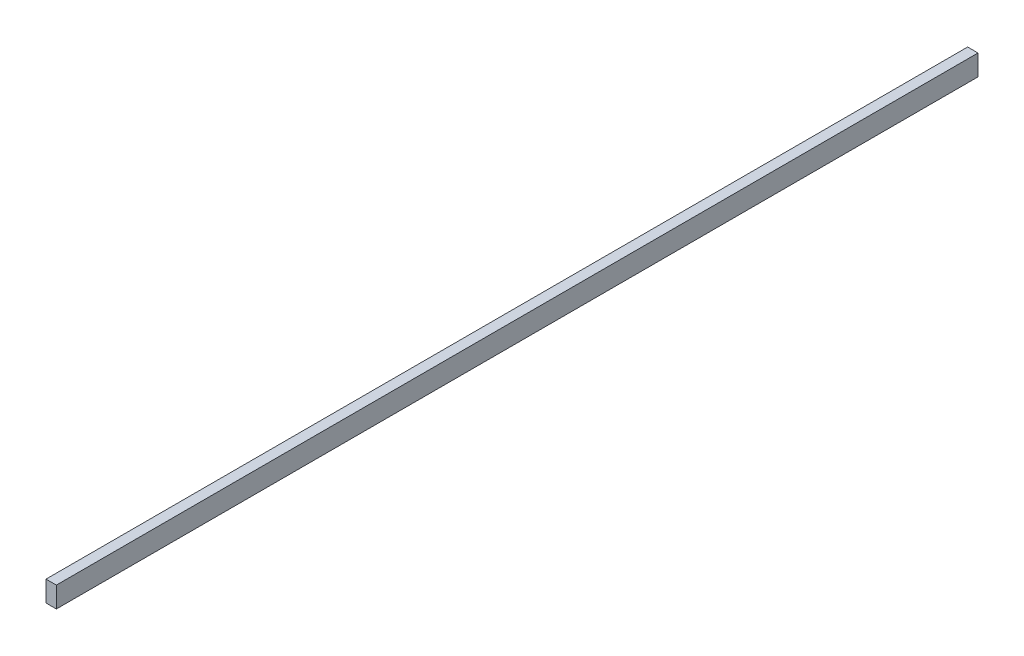
SolidWorks part; units mm, degrees
ref_plane "Ebene vorne" through (0, 0, 0) normal (0, 0, 1) x (1, 0, 0)
ref_plane "Ebene oben" through (0, 0, 0) normal (0, 1, 0) x (1, 0, 0)
ref_plane "Ebene rechts" through (0, 0, 0) normal (1, 0, 0) x (0, 0, -1)
sketch "Skizze1" plane through (0, 0, 0) normal (0, 0, 1) x (1, 0, 0)
  line L1 (0, 0) -> (5, 0)
  line L2 (0, 0) -> (0, 10)
  line L3 (0, 10) -> (5, 10)
  line L4 (5, 0) -> (5, 10)
  dimension "D1" = 5
  dimension "D2" = 10
extrude "Aufsatz-Linear austragen1" add sketch "Skizze1" along normal blind 445
